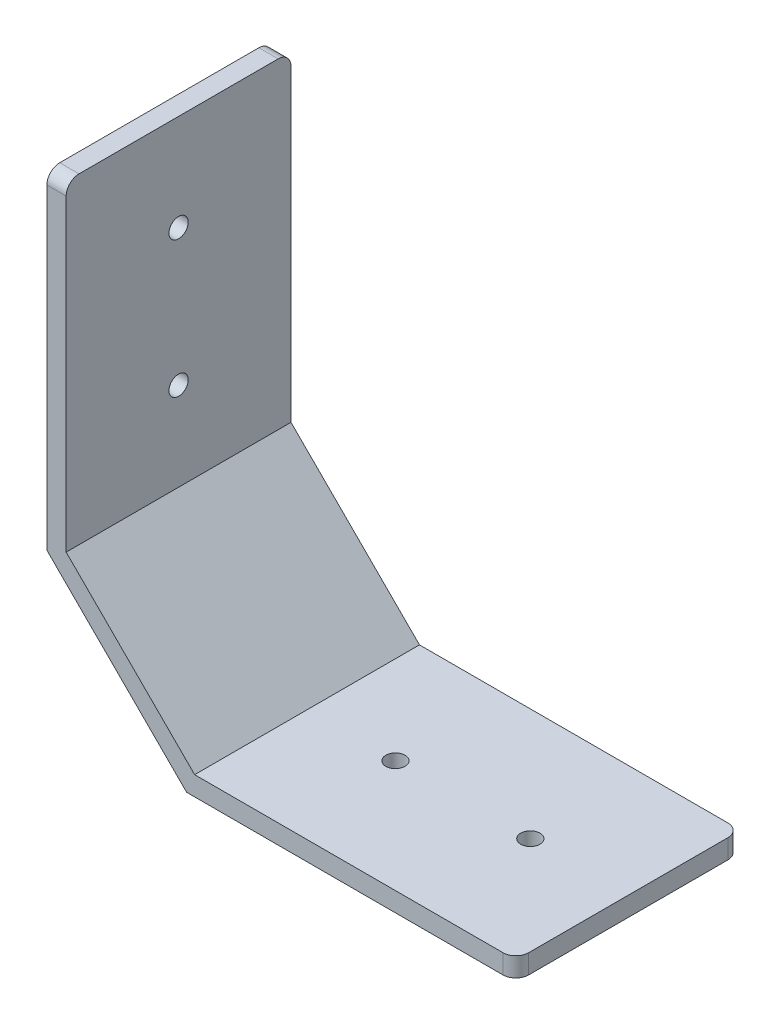
SolidWorks part; units mm, degrees
ref_plane "Plan de face" through (0, 0, 0) normal (0, 0, 1) x (1, 0, 0)
ref_plane "Plan de dessus" through (0, 0, 0) normal (0, 1, 0) x (1, 0, 0)
ref_plane "Plan de droite" through (0, 0, 0) normal (1, 0, 0) x (0, 0, -1)
sketch "Esquisse1" plane through (0, 0, 0) normal (0, 0, 1) x (1, 0, 0)
  line L0 (0, 0) -> (0, 50)
  line L1 (20, -20) -> (70, -20)
  line L2 (0, 0) -> (20, -20)
  dimension "D1" = 50
  dimension "D2" = 50
  dimension "D3" = 20
  dimension "D4" = 20
extrude "Extru.-Mince1" add sketch "Esquisse1" along normal blind 35 thin thin type one direction wall 3
fillet "Congé3" radius 2 1 edges at (-1.5, 50, 35)
fillet "Congé4" radius 2 1 edges at (-1.5, 50, 0)
fillet "Congé5" radius 2 1 edges at (70, -21.5, 35)
fillet "Congé6" radius 2 1 edges at (70, -21.5, 0)
sketch "Esquisse2" plane through (0, -23, 0) normal (0, -1, 0) x (1, 0, 0)
  line L0 (18.7574, 35) -> (68, 35) construction
  line L2 (18.7574, 35) -> (18.7574, 0) construction
  circle A0 centre (33.7574, 17.5) radius 1.5
  circle A1 centre (54.7574, 17.5) radius 1.5
  dimension "D1" = 3
  dimension "D2" = 3
  dimension "D3" = 17.5
  dimension "D4" = 17.5
  dimension "D5" = 21
  dimension "D6" = 15
extrude "Enlèv. mat.-Extru.1" cut sketch "Esquisse2" against normal blind 10
sketch "Esquisse3" plane through (-3, 0, 0) normal (-1, 0, 0) x (0, 0, 1)
  line L0 (0, 48) -> (0, -1.2426) construction
  line L1 (35, -1.2426) -> (0, -1.2426) construction
  line L2 (33, 50) -> (2, 50) construction
  circle A0 centre (17.5, 35) radius 1.5
  circle A1 centre (17.5, 13.7574) radius 1.5
  dimension "D1" = 3
  dimension "D2" = 3
  dimension "D3" = 17.5
  dimension "D4" = 17.5
  dimension "D5" = 15
  dimension "D6" = 15
extrude "Enlèv. mat.-Extru.2" cut sketch "Esquisse3" against normal blind 10
